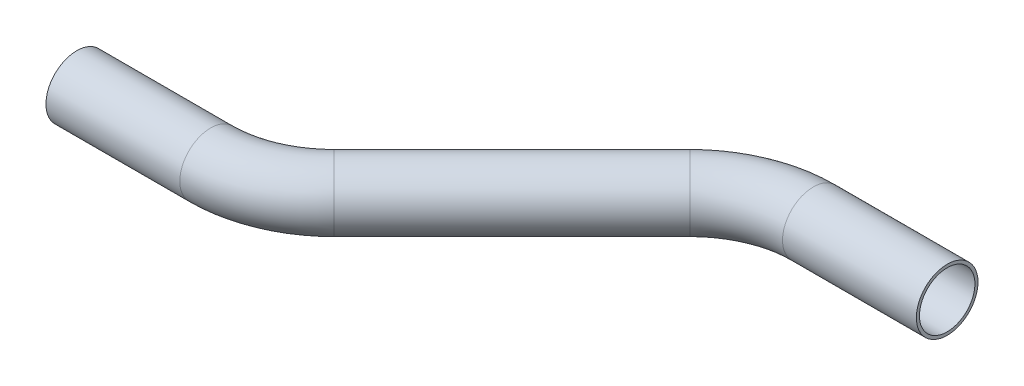
SolidWorks part; units mm, degrees
ref_plane "Front Plane" through (0, 0, 0) normal (0, 0, 1) x (1, 0, 0)
ref_plane "Top Plane" through (0, 0, 0) normal (0, 1, 0) x (1, 0, 0)
ref_plane "Right Plane" through (0, 0, 0) normal (1, 0, 0) x (0, 0, -1)
sketch "Sketch2" plane through (0, 0, 0) normal (0, 1, 0) x (1, 0, 0)
  line L0 (0, 0) -> (27.579, 0)
  line L1 (45.5395, 7.4395) -> (82.2225, 44.1225)
  line L2 (100.183, 51.562) -> (127.762, 51.562)
  arc A0 (82.2225, 44.1225) -> (100.183, 51.562) centre (100.183, 26.162) cw
  arc A1 (27.579, 0) -> (45.5395, 7.4395) centre (27.579, 25.4) ccw
  point P7 (89.662, 51.562)
  point P10 (38.1, 0)
  dimension "D5" = 25.4
  dimension "D1" = 38.1
  dimension "D2" = 38.1
  dimension "D3" = 51.562
  dimension "D4" = 135
ref_plane "Plane1" through (0, 0, 0) normal (1, 0, 0) x (0, 0, -1)
sketch "Sketch3" plane through (0, 0, 0) normal (1, 0, 0) x (0, 0, -1)
  circle A0 centre (0, 0) radius 6.35
  circle A1 centre (0, 0) radius 5.715
  dimension "D1" = 12.7
  dimension "D2" = 0.635
sweep "Sweep1" add profiles "Sketch3" path "Sketch2"
